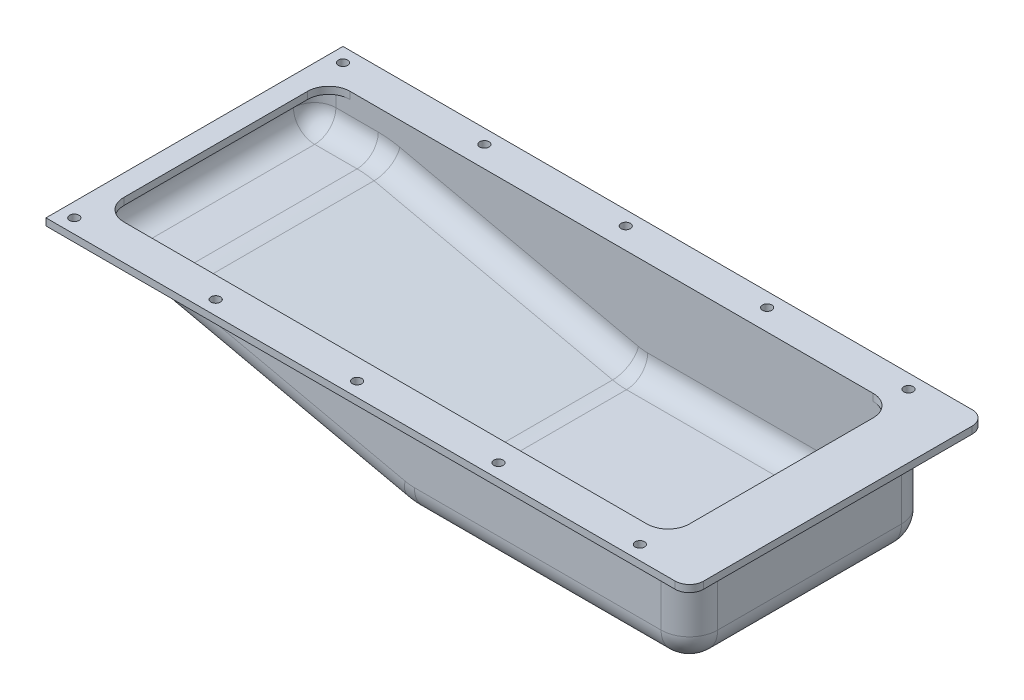
SolidWorks part; units mm, degrees
material "Plain Carbon Steel"
ref_plane "Front Plane" through (0, 0, 0) normal (0, 0, 1) x (1, 0, 0)
ref_plane "Top Plane" through (0, 0, 0) normal (0, 1, 0) x (1, 0, 0)
ref_plane "Right Plane" through (0, 0, 0) normal (1, 0, 0) x (0, 0, -1)
sketch "Sketch1" plane through (0, 0, 0) normal (0, 1, 0) x (-1, 0, 0)
  line L1 (-210, 35) -> (-210, -35)
  line L2 (-210, 105) -> (245, 105)
  line L3 (-170, 35) -> (-170, -35)
  line L4 (245, 105) -> (245, -105)
  line L6 (245, -105) -> (-210, -105)
  line L10 (-155, 80) -> (215, 80)
  line L11 (-170, 65) -> (-170, 35)
  line L12 (-155, -80) -> (215, -80)
  line L13 (230, 65) -> (230, -65)
  line L15 (-210, 105) -> (-210, 35)
  line L17 (-210, 35) -> (-170, 35) construction
  line L18 (-210, -105) -> (-210, -35)
  line L20 (-210, -35) -> (-170, -35) construction
  line L21 (-170, -35) -> (-170, -65)
  arc A0 (-155, 80) -> (-170, 65) centre (-155, 65) ccw
  arc A1 (-170, -65) -> (-155, -80) centre (-155, -65) ccw
  arc A2 (215, 80) -> (230, 65) centre (215, 65) cw
  arc A3 (215, -80) -> (230, -65) centre (215, -65) ccw
  point P0 (230, 0)
  point P2 (-190, 35)
  dimension "D9" = 15
  dimension "D1" = 230
  dimension "D2" = 400
  dimension "D3" = 25
  dimension "D4" = 40
  dimension "D5" = 25
  dimension "D6" = 15
  dimension "D7" = 210
  dimension "D8" = 70
sketch "Sketch4" plane through (0, 0, 0) normal (0, 0, 1) x (1, 0, 0)
  line L0 (-245, 0) -> (-245, -10)
  line L1 (210, 0) -> (-245, 0) construction
  line L2 (-225, -30) -> (-195, -30)
  line L5 (190, -50) -> (190, 0)
  line L6 (190, 0) -> (-245, 0)
  line L8 (170, -70) -> (-4.4964, -70)
  line L9 (-15.3719, -68.8029) -> (-184.1245, -31.1971)
  arc A1 (-195, -30) -> (-184.1245, -31.1971) centre (-195, -80) cw
  arc A2 (170, -70) -> (190, -50) centre (170, -50) ccw
  arc A4 (-245, -10) -> (-225, -30) centre (-225, -10) ccw
  arc A5 (-4.4964, -70) -> (-15.3719, -68.8029) centre (-4.4964, -20) cw
  point P13 (-195, -30)
  point P16 (-195, -10)
  point P19 (190, -70)
  point P22 (-10, -70)
  point P25 (-245, -30)
  point P32 (-10, -70)
  dimension "D8" = 20
  dimension "D9" = 20
  dimension "D10" = 50
  dimension "D11" = 50
  dimension "D1" = 0
  dimension "D2" = 20
  dimension "D3" = 70
  dimension "D4" = 30
  dimension "D5" = 200
  dimension "D6" = 50
  dimension "D7" = 20
extrude "Boss-Extrude2" add sketch "Sketch4" along normal blind 85 and the other way blind 85
fillet "Fillet1" radius 20 18 edges at (-189.5294, -30.3002, -85) (-189.5294, -30.3002, 85) (190, -25, -85) (184.1421, -64.1421, -85) (82.7518, -70, -85) (-99.7482, -50, -85) (-210, -30, -85) (-239.1421, -24.1421, -85) (190, -25, 85) (184.1421, -64.1421, 85) (82.7518, -70, 85) (-99.7482, -50, 85) (-210, -30, 85) (-239.1421, -24.1421, 85) (-245, -5, -85) (-245, -5, 85) (-9.967, -69.6998, -85) (-9.967, -69.6998, 85)
shell "Shell1" thickness 5 removed face at (-27.5, 0, 0)
extrude "Boss-Extrude3" add sketch "Sketch1" along normal blind 5
sketch "Sketch5" plane through (0, 5, 0) normal (0, 1, 0) x (-1, 0, 0)
  line L0 (245, -105) -> (245, 105) construction
  line L2 (245, 105) -> (-210, 105) construction
  line L7 (-210, 35) -> (-170, 35) construction
  line L8 (-210, -35) -> (-170, -35) construction
  circle A0 centre (-165, 95) radius 3
  circle A1 centre (-65, 95) radius 3
  circle A2 centre (135, 95) radius 3
  circle A3 centre (235, 95) radius 3
  circle A4 centre (-165, -95) radius 3
  circle A5 centre (-65, -95) radius 3
  circle A6 centre (135, -95) radius 3
  circle A7 centre (235, -95) radius 3
  circle A8 centre (35, 95) radius 3
  circle A9 centre (35, -95) radius 3
  circle A10 centre (-165, 27) radius 3
  circle A11 centre (-165, -27) radius 3
  point P32 (-190, -35)
  dimension "D1" = 6
  dimension "D2" = 190
  dimension "D3" = 10
  dimension "D4" = 100
  dimension "D5" = 10
  dimension "D10" = 8
  dimension "D6" = 100
  dimension "D7" = 100
  dimension "D8" = 100
  dimension "D9" = 8
hole_wizard "M6 Clearance Hole1" positions "Sketch6" profile "Sketch7" hole size "M6" standard "ISO" end condition through all
sketch "Sketch6" plane through (0, 5, 0) normal (0, 1, 0) x (1, 0, 0)
  point P0 (165, -95)
  point P3 (65, -95)
  point P6 (-35, -95)
  point P9 (-135, -95)
  point P12 (-235, -95)
  point P15 (-235, 95)
  point P18 (-135, 95)
  point P21 (-35, 95)
  point P24 (65, 95)
  point P27 (165, 95)
sketch "Sketch7" plane through (165, 5, 95) normal (1, 0, 0) x (0, 0, 1)
  line L0 (0, 0) -> (0, 75)
  line L1 (0, 75) -> (3.3, 75)
  line L2 (3.3, 75) -> (3.3, 0)
  line L5 (3.3, 0) -> (0, 0)
  line L11 (0, -6.35) -> (0, 107.95) construction
  dimension "Thru Hole Dia." = 6.6
  dimension "Thru Hole Depth" = 75
fillet "Fillet2" radius 10 2 edges at (210, 2.5, -105) (210, 2.5, 105)
